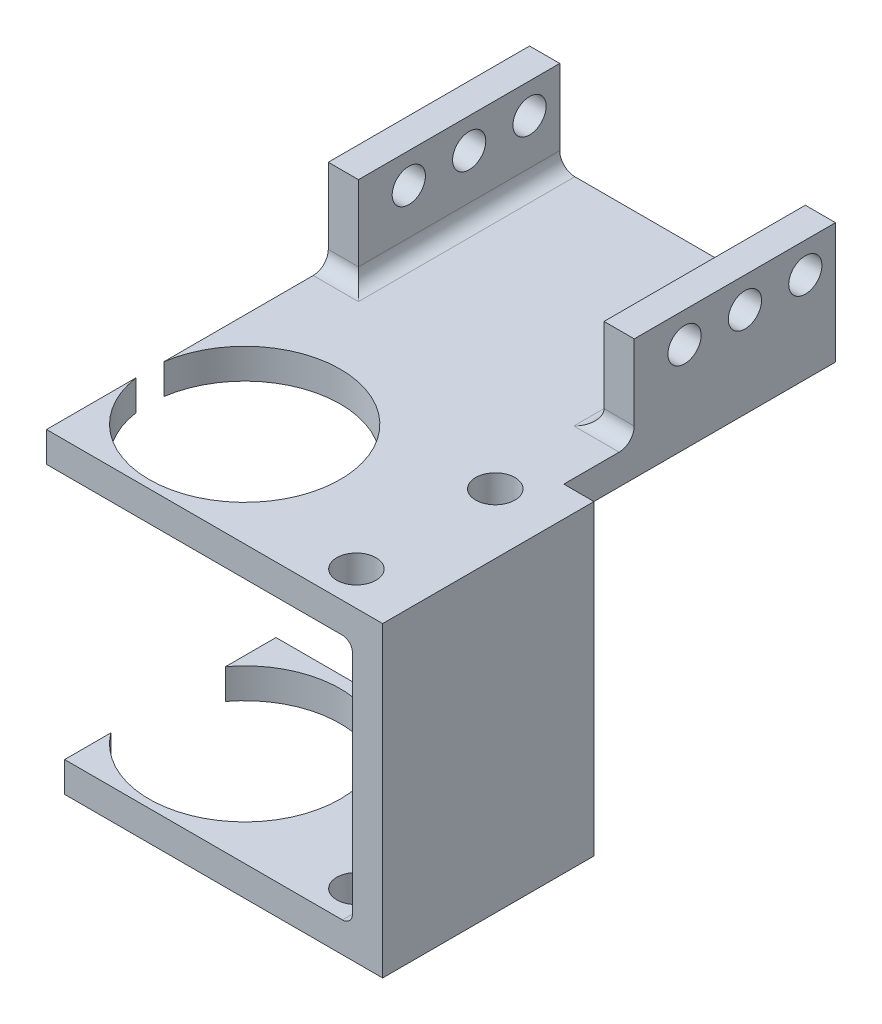
SolidWorks part; units mm, degrees
ref_plane "Front Plane" through (0, 0, 0) normal (0, 0, 1) x (1, 0, 0)
ref_plane "Top Plane" through (0, 0, 0) normal (0, 1, 0) x (1, 0, 0)
ref_plane "Right Plane" through (0, 0, 0) normal (1, 0, 0) x (0, 0, -1)
sketch "Sketch1" plane through (0, 0, 0) normal (0, 0, 1) x (1, 0, 0)
  line L2 (11.421, -21) -> (14.421, -21)
  line L3 (11.421, -21) -> (11.421, -30)
  line L5 (14.421, -21) -> (14.421, -33)
  line L6 (14.3773, -33) -> (14.421, -33)
  line L7 (11.421, -30) -> (-12.979, -30)
  line L12 (-15.979, -33) -> (-15.979, -21)
  line L13 (-15.979, -21) -> (-12.979, -21)
  line L14 (-12.979, -30) -> (-12.979, -21)
  line L16 (14.421, -33) -> (-15.979, -33)
  line L21 (-11.479, -27) -> (-8.779, -27) construction
  line L28 (14.421, -21) -> (14.421, -33)
  line L31 (-12.979, -30) -> (-15.979, -30)
  line L32 (11.421, -30) -> (14.421, -30)
  line L35 (11.021, -23.0615) -> (11.021, 5.0615) construction
  line L36 (-12.979, -23.0615) -> (-12.979, 5.0615) construction
  dimension "D1" = 3
  dimension "D2" = 3
  dimension "D3" = 3
  dimension "D4" = 0.4
  dimension "D5" = 9
  dimension "D7" = 3
extrude "Boss-Extrude1" add sketch "Sketch1" against normal blind 27 contours L32 L7 L31 L12 L16 L6 L28 | L31 L14 L13 L12 | L3 L32 L5 L2 region at (12.921, -25.5, 0) region at (-0.779, -31.5, 0) region at (-14.479, -25.5, 0)
extrude "Boss-Extrude2" add sketch "Sketch1<3>" along normal blind 21 contours L32 L7 L31 L12 L16 L6 L28 region at (-0.779, -31.5, 0)
sketch "Sketch1<3>" plane through (0, 0, 0) normal (0, 0, 1) x (1, 0, 0) same geometry as "Sketch1"
sketch "Sketch5" plane through (0, 0, 21) normal (0, 0, 1) x (1, 0, 0)
  line L0 (14.421, -30) -> (17.421, -30)
  line L1 (17.421, -30) -> (17.421, -60.5)
  line L2 (17.421, -60.5) -> (-14.176, -60.5)
  line L3 (-14.176, -60.5) -> (-14.176, -57.5)
  line L4 (-14.176, -57.5) -> (14.421, -57.5)
  line L5 (14.421, -57.5) -> (14.421, -30)
  line L6 (14.421, -33) -> (-15.979, -33) construction
  dimension "D1" = 3
  dimension "D2" = 3
  dimension "D3" = 24.5
extrude "Boss-Extrude3" add sketch "Sketch5" against normal blind 21
sketch "Sketch6" plane through (0, -60.5, 0) normal (0, -1, 0) x (1, 0, 0)
  line L0 (9.0704, -4.9651) -> (37.4704, -4.9651) construction
  line L1 (17.421, 0) -> (17.421, 21) construction
  circle A0 centre (-6.579, 10.7072) radius 9.5
  dimension "D1" = 24
extrude "Cut-Extrude1" cut sketch "Sketch6" against normal through all both and the other way through all
hole_wizard "M3.5 Clearance Hole1" positions "Sketch7" profile "Sketch8" hole size "M3.5" standard "ANSI Metric" end condition through all
sketch "Sketch7" plane through (0, -60.5, 0) normal (0, -1, 0) x (-1, 0, 0)
  line L0 (6.579, -10.7072) -> (-24.9882, -10.7072) construction
  arc A0 (14.176, -5.0031) -> (14.176, -16.4112) centre (6.579, -10.7072) ccw construction
  arc A1 (14.176, -5.0031) -> (14.176, -16.4112) centre (6.579, -10.7072) ccw
  point P0 (-11.421, -17.6072)
  point P14 (-11.421, -3.8072)
  dimension "D1" = 18
  dimension "D2" = 6.9
sketch "Sketch8" plane through (11.421, -60.5, 17.6072) normal (1, 0, 0) x (0, 0, -1)
  line L0 (0, 0) -> (0, 39.5)
  line L1 (0, 39.5) -> (1.95, 39.5)
  line L2 (1.95, 39.5) -> (1.95, 0.025)
  line L3 (1.95, 0.025) -> (1.975, 0)
  line L5 (1.975, 0) -> (0, 0)
  line L6 (-1.95, 0.025) -> (-1.975, 0) construction
  line L11 (0, -6.35) -> (0, 107.95) construction
  dimension "Thru Hole Dia." = 3.9
  dimension "Thru Hole Depth" = 39.5
  dimension "Near C'Sink Dia." = 3.95
  dimension "Near C'Sink Angle" = 90
fillet "Fillet1" radius 1 2 edges at (14.421, -33, 10.5) (14.421, -57.5, 10.5)
ref_plane "Plane1" through (0, 0, 10) normal (0, 0, -1) x (-1, 0, 0)
sketch "Sketch14" plane through (0, 0, 10) normal (0, 0, -1) x (-1, 0, 0)
  line L0 (-14.421, -45.25) -> (-11.421, -33)
  line L1 (-14.421, -34) -> (-14.421, -56.5) construction
  line L3 (-14.421, -33) -> (15.979, -33) construction
  line L4 (-14.421, -45.25) -> (0.3314, -45.25) construction
  dimension "D1" = 3
rib "Rib16" sketch "Sketch14" sketch "Sketch14" thickness 2 extrusion direction parallel to sketch draft on no parameters "D1"=2
sketch "Sketch16" plane through (0, 0, 10) normal (0, 0, 1) x (1, 0, 0)
  line L0 (14.421, -45.25) -> (11.421, -57.5)
  line L2 (13.421, -57.5) -> (-14.176, -57.5) construction
  line L4 (14.421, -34) -> (14.421, -56.5) construction
  dimension "D1" = 3
rib "Rib17" sketch "Sketch16" sketch "Sketch16" thickness 2 extrusion direction parallel to sketch draft on no parameters "D1"=2
fillet "Fillet2" radius 1.5 2 edges at (11.421, -30, -13.5) (-12.979, -30, -13.5)
sketch "Sketch18" plane through (-15.979, 0, 0) normal (-1, 0, 0) x (0, 0, 1)
  line L1 (-27, -33) -> (-27, -21) construction
  line L2 (-27, -21) -> (0, -21) construction
  line L4 (0, -21) -> (-7, -21)
  line L5 (0, -21) -> (0, -30)
  line L6 (0, -30) -> (-7, -30)
  line L7 (-7, -21) -> (-7, -30)
  line L8 (0, -30) -> (0, -21) construction
  circle A0 centre (-18, -24) radius 1.65
  circle A1 centre (-12, -24) radius 1.65
  circle A2 centre (-24, -24) radius 1.65
  point P2 (0, -21)
  dimension "D1" = 6
  dimension "D2" = 6
  dimension "D3" = 3
  dimension "D4" = 3
  dimension "D5" = 7
extrude "Cut-Extrude2" cut sketch "Sketch18" against normal through all
fillet "Fillet3" radius 1.5 2 edges at (12.171, -30, -7) (-13.729, -30, -7)
